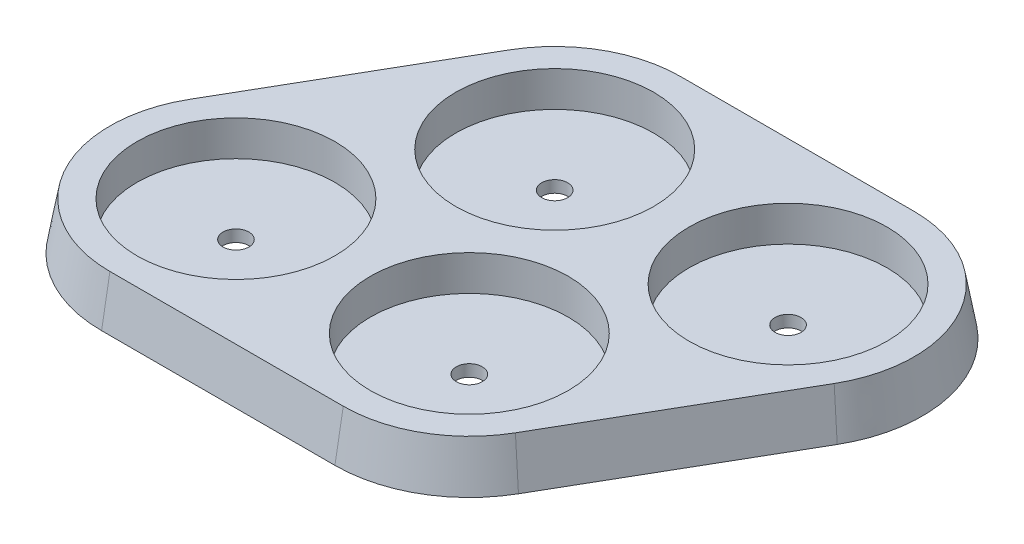
SolidWorks part; units mm, degrees
note: The reader was unsure of these and kept them because the rebuilt part matched: shared geometry of "Sketch1<3>", "Sketch1<4>".
ref_plane "Front Plane" through (0, 0, 0) normal (0, 0, 1) x (1, 0, 0)
ref_plane "Top Plane" through (0, 0, 0) normal (0, 1, 0) x (1, 0, 0)
ref_plane "Right Plane" through (0, 0, 0) normal (1, 0, 0) x (0, 0, -1)
sketch "Sketch1" plane through (0, 0, 0) normal (0, 1, 0) x (1, 0, 0)
  line L0 (0, 0) -> (-9.9, -17.1473) construction
  line L1 (-9.9, -17.1473) -> (-19.8, 0) construction
  line L2 (-19.8, 0) -> (0, 0) construction
  line L3 (9.8727, -5.7) -> (-0.0273, -22.8473)
  line L4 (-9.9, -28.5473) -> (-29.7, -28.5473)
  line L5 (0, 11.4) -> (-19.8, 11.4)
  line L6 (-9.9, -17.1473) -> (-29.7, -17.1473) construction
  line L7 (-29.7, -17.1473) -> (-19.8, 0) construction
  line L8 (-39.5727, -11.4473) -> (-29.6727, 5.7)
  circle A0 centre (0, 0) radius 8.4
  circle A1 centre (-19.8, 0) radius 8.4
  circle A2 centre (-9.9, -17.1473) radius 8.4
  circle A3 centre (-9.9, -17.1473) radius 1.1
  circle A4 centre (-19.8, 0) radius 1.1
  circle A5 centre (0, 0) radius 1.1
  circle A6 centre (-9.9, -17.1473) radius 11.4
  circle A7 centre (-19.8, 0) radius 11.4
  circle A8 centre (0, 0) radius 11.4
  circle A9 centre (-29.7, -17.1473) radius 1.1
  circle A10 centre (-29.7, -17.1473) radius 8.4
  circle A11 centre (-29.7, -17.1473) radius 11.4
  dimension "D1" = 16.8
  dimension "D4" = 16.8
  dimension "D5" = 16.8
  dimension "D7" = 2.2
  dimension "D8" = 2.2
  dimension "D9" = 2.2
  dimension "D10" = 22.8
  dimension "D11" = 22.8
  dimension "D12" = 22.8
  dimension "D14" = 2.2
  dimension "D15" = 16.8
  dimension "D16" = 22.8
  dimension "D2" = 60
  dimension "D3" = 60
  dimension "D6" = 19.8
  dimension "D13" = 60
extrude "Boss-Extrude1" add sketch "Sketch1" along normal blind 4 draft 10
extrude "Cut-Extrude1" cut sketch "Sketch1<3>" against normal blind 4 from surface at 4 contours A3 | A5 | A9 | A4 starting at face at (-14.85, 4, 8.5737)
sketch "Sketch1<3>" plane through (0, 0, 0) normal (0, 1, 0) x (1, 0, 0) same geometry as "Sketch1"
extrude "Cut-Extrude2" cut sketch "Sketch1<4>" against normal blind 3 from surface at 4 contours A1 A4 | A2 A3 | A0 A5 | A10 A9 starting at face at (0, 4, 1.1)
sketch "Sketch1<4>" plane through (0, 0, 0) normal (0, 1, 0) x (1, 0, 0) same geometry as "Sketch1"
